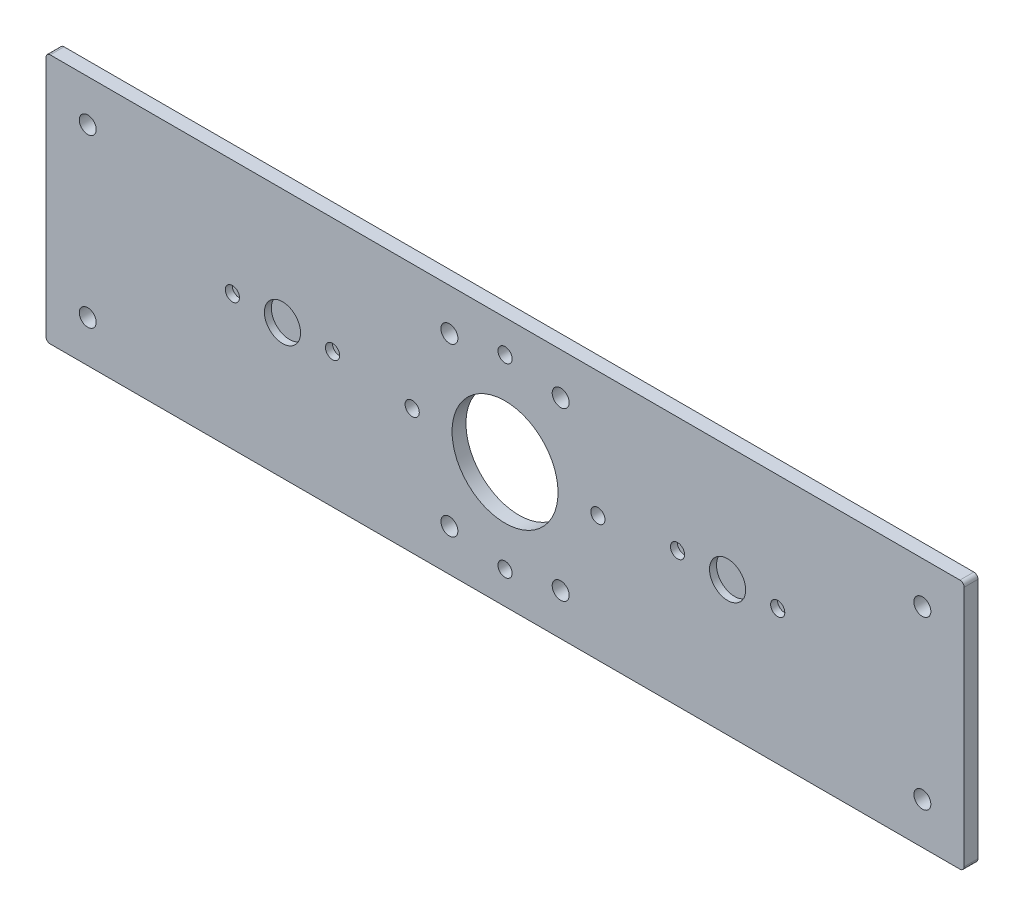
SolidWorks part; units mm, degrees
ref_plane "Front Plane" through (0, 0, 0) normal (0, 0, 1) x (1, 0, 0)
ref_plane "Top Plane" through (0, 0, 0) normal (0, 1, 0) x (1, 0, 0)
ref_plane "Right Plane" through (0, 0, 0) normal (1, 0, 0) x (0, 0, -1)
sketch "Sketch1" plane through (0, 0, 0) normal (0, 0, 1) x (1, 0, 0)
  line L0 (-165, 0) -> (165, 0) construction
  line L1 (165, -45) -> (-165, -45)
  line L2 (165, -45) -> (165, 45)
  line L3 (165, 45) -> (-165, 45)
  line L4 (-165, -45) -> (-165, 45)
  line L5 (165, -45) -> (-165, 45) construction
  line L6 (165, 45) -> (-165, -45) construction
  line L8 (0, -33.3754) -> (33.3754, 0) construction
  line L9 (0, -33.3754) -> (-33.3754, 0) construction
  line L10 (-33.3754, 0) -> (0, 33.3754) construction
  line L11 (33.3754, 0) -> (0, 33.3754) construction
  line L12 (0, -33.3754) -> (0, 33.3754) construction
  line L13 (-33.3754, 0) -> (33.3754, 0) construction
  circle A0 centre (0, 0) radius 19.05
  circle A1 centre (-33.3754, 0) radius 2.55
  circle A2 centre (33.3754, 0) radius 2.55
  circle A3 centre (0, 33.3754) radius 2.55
  circle A4 centre (0, -33.3754) radius 2.55
  point P0 (0, 0)
  dimension "D3" = 38.1
  dimension "D4" = 47.2
  dimension "D5" = 47.2
  dimension "D8" = 5.1
  dimension "D9" = 5.1
  dimension "D10" = 5.1
  dimension "D11" = 5.1
  dimension "D1" = 90
  dimension "D2" = 330
  dimension "D6" = 90
  dimension "D7" = 90
extrude "Boss-Extrude1" add sketch "Sketch1" along normal mid plane 5
sketch "Sketch2" plane through (0, 0, 2.5) normal (0, 0, 1) x (1, 0, 0)
  line L2 (-150, 45) -> (-150, -45)
  line L3 (-150, 45) -> (-150, -45) construction
  line L5 (150, -45) -> (150, 45)
  line L6 (150, -45) -> (150, 45) construction
  line L23 (165, 30) -> (-165, 30)
  line L24 (165, 30) -> (-165, 30) construction
  line L25 (0, 45) -> (0, -45) construction
  line L26 (-165, -30) -> (165, -30)
  line L27 (-165, -30) -> (165, -30) construction
  line L28 (165, 45) -> (-165, 45) construction
  line L29 (-165, -45) -> (165, -45) construction
  line L30 (-20, 45) -> (-20, -45) construction
  line L31 (20, 45) -> (20, -45) construction
  circle A0 centre (-150, 30) radius 3.05
  circle A1 centre (-150, -30) radius 3.05
  circle A2 centre (-20, 30) radius 3.05
  circle A3 centre (-20, -30) radius 3.05
  circle A4 centre (20, -30) radius 3.05
  circle A5 centre (20, 30) radius 3.05
  circle A6 centre (150, 30) radius 3.05
  circle A7 centre (150, -30) radius 3.05
  dimension "D7" = 6.1
  dimension "D8" = 6.1
  dimension "D9" = 6.1
  dimension "D10" = 6.1
  dimension "D11" = 6.1
  dimension "D12" = 6.1
  dimension "D13" = 6.1
  dimension "D14" = 6.1
  dimension "D1" = 15
  dimension "D2" = 15
  dimension "D3" = 15
  dimension "D4" = 15
  dimension "D5" = 20
  dimension "D6" = 20
extrude "Cut-Extrude1" cut sketch "Sketch2" against normal through all
sketch "Sketch3" plane through (0, 0, 2.5) normal (0, 0, 1) x (1, 0, 0)
  line L0 (0, 3.4) -> (-49.4534, 3.4) construction
  circle A0 centre (-62, 3.4) radius 2.55
  circle A1 centre (-98, 3.4) radius 2.55
  circle A2 centre (-80, 3.4) radius 6.5
  dimension "D1" = 5.1
  dimension "D2" = 5.1
  dimension "D3" = 13
  dimension "D4" = 80
  dimension "D5" = 18
  dimension "D6" = 18
  dimension "D7" = 3.4
extrude "Cut-Extrude2" cut sketch "Sketch3" against normal up to vertex (2.5 mm away) up to point (0, 0, 0)
mirror "Mirror1" about plane through (0, 0, 0) normal (1, 0, 0) of "Cut-Extrude2"
fillet "Fillet1" radius 1.5 4 edges at (-165, -45, 0) (165, -45, 0) (165, 45, 0) (-165, 45, 0)
equation "\"D4@Sketch3\"=160/2"
equation "\"D9@Sketch2\"=\"D7@Sketch2\""
equation "\"D12@Sketch2\"=\"D7@Sketch2\""
equation "\"D13@Sketch2\"=\"D7@Sketch2\""
equation "\"D8@Sketch2\"=\"D7@Sketch2\""
equation "\"D10@Sketch2\"=\"D7@Sketch2\""
equation "\"D11@Sketch2\"=\"D7@Sketch2\""
equation "\"D14@Sketch2\"=\"D7@Sketch2\""
equation "\"D9@Sketch1\"=\"D8@Sketch1\""
equation "\"D10@Sketch1\"=\"D8@Sketch1\""
equation "\"D11@Sketch1\"=\"D8@Sketch1\""
